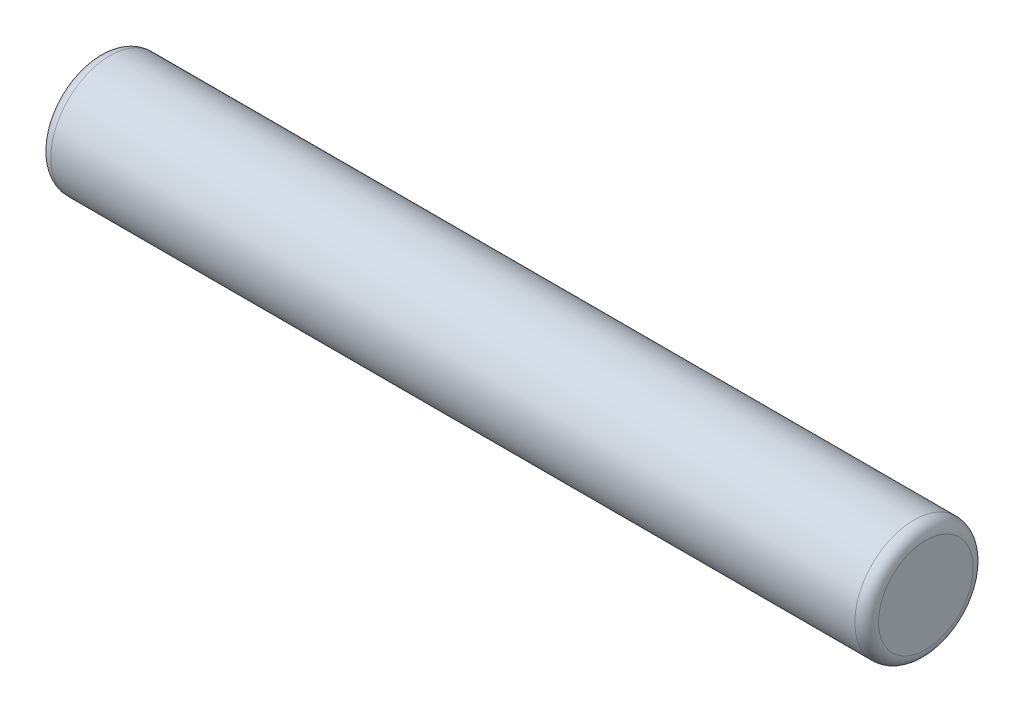
SolidWorks part; units mm, degrees
ref_plane "Vorne" through (0, 0, 0) normal (0, 0, 1) x (1, 0, 0)
ref_plane "Oben" through (0, 0, 0) normal (0, 1, 0) x (1, 0, 0)
ref_plane "Rechts" through (0, 0, 0) normal (1, 0, 0) x (0, 0, -1)
ref_plane "E_Boden" through (0, 1, 0) normal (0, 1, 0) x (1, 0, 0)
sketch "Skizze1" plane through (0, 0, 0) normal (1, 0, 0) x (0, 0, -1)
  circle A0 centre (0, 0) radius 5
  dimension "D1" = 10
extrude "Aufsatz-Linear austragen1" add sketch "Skizze1" along normal blind 70
fillet "Verrundung3" radius 1 2 edges at (0, 0, -5) (70, 0, -5)
